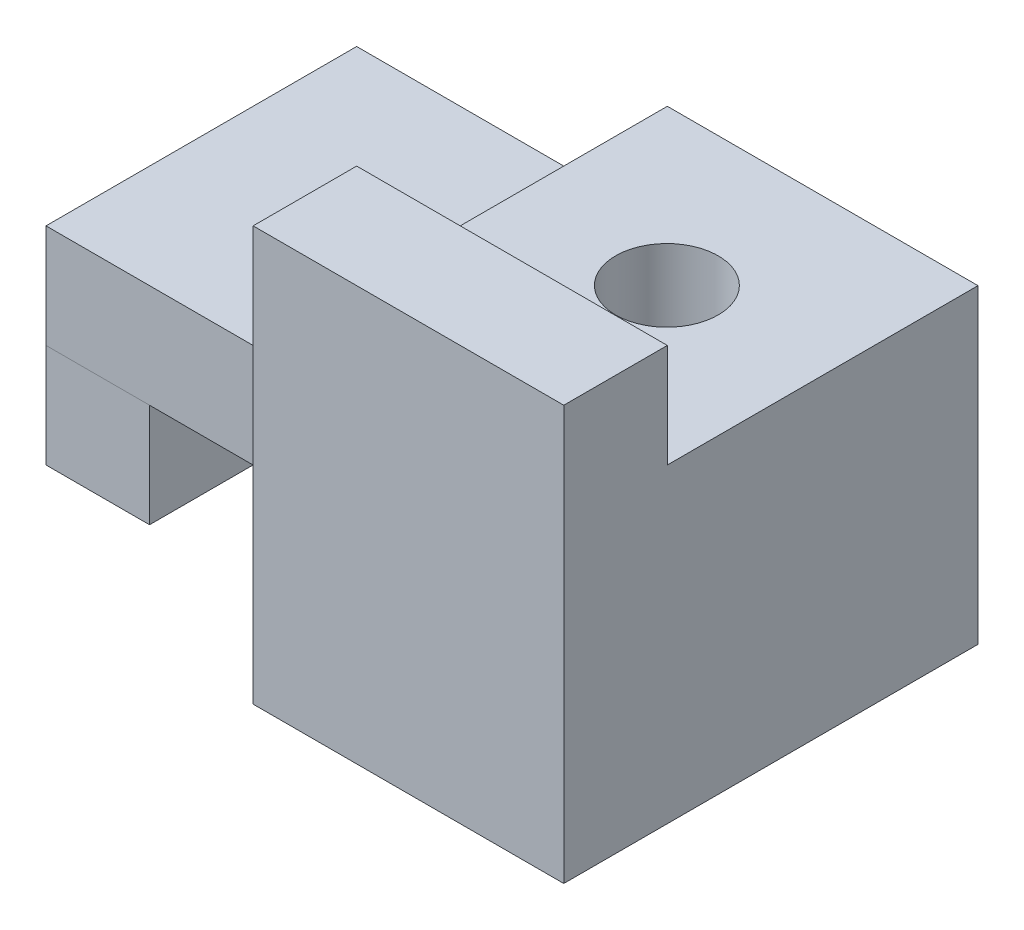
SolidWorks part; units mm, degrees
ref_plane "Front Plane" through (0, 0, 0) normal (0, 0, 1) x (1, 0, 0)
ref_plane "Top Plane" through (0, 0, 0) normal (0, 1, 0) x (1, 0, 0)
ref_plane "Right Plane" through (0, 0, 0) normal (1, 0, 0) x (0, 0, -1)
sketch "Sketch1" plane through (0, 0, 0) normal (0, 1, 0) x (1, 0, 0)
  line L0 (0, 0) -> (0, 76.2)
  line L1 (0, 76.2) -> (76.2, 76.2)
  line L2 (76.2, 76.2) -> (76.2, 0)
  line L3 (76.2, 0) -> (0, 0)
extrude "Boss-Extrude1" add sketch "Sketch1" along normal blind 25.4
sketch "Sketch2" plane through (0, 25.4, 0) normal (0, 1, 0) x (1, 0, 0)
  line L1 (76.2, 76.2) -> (152.4, 76.2)
  line L2 (76.2, 76.2) -> (76.2, -25.4)
  line L3 (76.2, -25.4) -> (152.4, -25.4)
  line L4 (152.4, 76.2) -> (152.4, -25.4)
extrude "Boss-Extrude2" add sketch "Sketch2" along normal blind 25.4 and the other way blind 25.4
sketch "Sketch3" plane through (0, 0, 0) normal (0, -1, 0) x (1, 0, 0)
  line L0 (152.4, -76.2) -> (0, -76.2) construction
  line L1 (0, 0) -> (25.4, 0)
  line L2 (0, 0) -> (0, -76.2)
  line L3 (0, -76.2) -> (25.4, -76.2)
  line L4 (25.4, 0) -> (25.4, -76.2)
extrude "Boss-Extrude3" add sketch "Sketch3" along normal blind 25.4 separate body
sketch "Sketch4" plane through (0, 50.8, 0) normal (0, 1, 0) x (1, 0, 0)
  line L0 (152.4, -25.4) -> (152.4, 76.2) construction
  line L1 (76.2, -25.4) -> (152.4, -25.4)
  line L2 (76.2, -25.4) -> (76.2, 0)
  line L3 (76.2, 0) -> (152.4, 0)
  line L4 (152.4, -25.4) -> (152.4, 0)
extrude "Boss-Extrude4" add sketch "Sketch4" along normal blind 25.4
sketch "Sketch5" plane through (0, 0, 0) normal (0, -1, 0) x (1, 0, 0)
  line L1 (76.2, 25.4) -> (152.4, 25.4)
  line L2 (76.2, 25.4) -> (76.2, -76.2)
  line L3 (76.2, -76.2) -> (152.4, -76.2)
  line L4 (152.4, 25.4) -> (152.4, -76.2)
extrude "Boss-Extrude5" add sketch "Sketch5" along normal blind 25.4
sketch "Sketch6" plane through (0, 25.4, 0) normal (0, 1, 0) x (1, 0, 0)
  circle A0 centre (50.8174, 37.992) radius 12.7627
  point P0 (0, 0)
sketch "Sketch7" plane through (0, 50.8, 0) normal (0, 1, 0) x (1, 0, 0)
  circle A0 centre (114.192, 38.1) radius 12.5776
  point P0 (0, 0)
extrude "Cut-Extrude1" cut sketch "Sketch7" against normal blind 76.2
extrude "Cut-Extrude2" cut sketch "Sketch6" against normal blind 25.4
